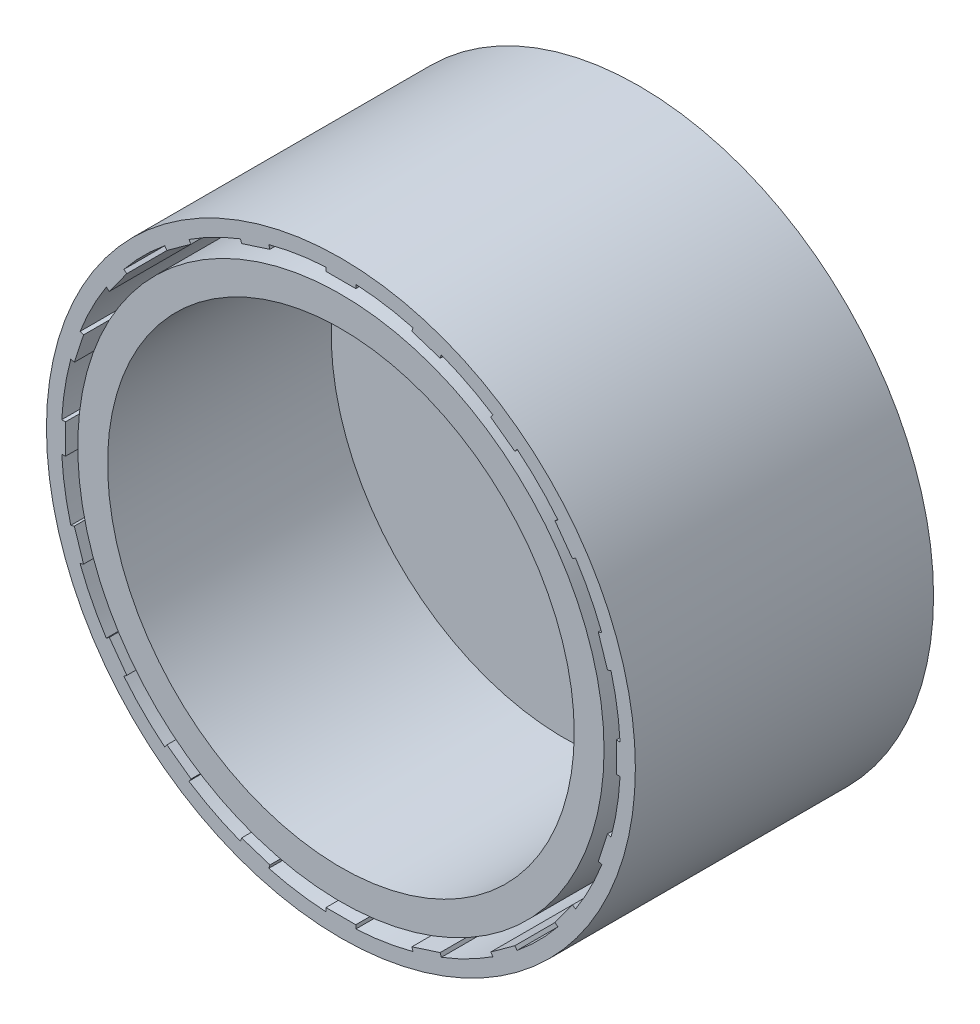
SolidWorks part; units mm, degrees
ref_plane "Front Plane" through (0, 0, 0) normal (0, 0, 1) x (1, 0, 0)
ref_plane "Top Plane" through (0, 0, 0) normal (0, 1, 0) x (1, 0, 0)
ref_plane "Right Plane" through (0, 0, 0) normal (1, 0, 0) x (0, 0, -1)
sketch "Sketch1" plane through (0, 0, 0) normal (0, 0, 1) x (1, 0, 0)
  circle A0 centre (0, 0) radius 18.75
  circle A1 centre (0, 0) radius 17.65
  circle A2 centre (0, 0) radius 4.625
  circle A3 centre (0, 0) radius 1.625
  circle A4 centre (0, 0) radius 19.75
  circle A5 centre (0, 0) radius 15.65
  dimension "D1" = 3.25
  dimension "D2" = 3
  dimension "D3" = 39.5
  dimension "D4" = 1
  dimension "D5" = 1.1
  dimension "D6" = 2
extrude "Boss-Extrude1" add sketch "Sketch1" against normal blind 10 contours A2 A3 region at (-4.4942, 0, 0)
extrude "Boss-Extrude2" add sketch "Sketch1<3>" along normal blind 5 separate body contours A1 A2 | A0 A1 | A4 A0 | A5 A2 | A2 A3 region at (-18.2197, 0, 0) region at (-17.1508, 0, 0) region at (-4.4942, 0, 0) region at (-19.1914, 0, 0) region at (-15.2074, 0, 0)
sketch "Sketch1<3>" plane through (0, 0, 0) normal (0, 0, 1) x (1, 0, 0) same geometry as "Sketch1"
extrude "Boss-Extrude3" add sketch "Sketch1<4>" along normal blind 20 contours A1 A2 | A4 A0 region at (-17.1508, 0, 0) region at (-19.1914, 0, 0)
sketch "Sketch1<4>" plane through (0, 0, 0) normal (0, 0, 1) x (1, 0, 0) same geometry as "Sketch1"
sketch "Sketch2" plane through (0, 0, 0) normal (0, 0, 1) x (1, 0, 0)
  line L0 (4.7575, 17.8782) -> (6.6596, 17.2601)
  line L1 (-1, 18.4733) -> (1, 18.4733)
  line L2 (-1, 18.4733) -> (-1, 18.7233)
  line L3 (-1, 18.7233) -> (1, 18.7233) construction
  line L4 (1, 18.4733) -> (1, 18.7233)
  line L5 (-1, 18.4733) -> (1, 18.7233) construction
  line L6 (-1, 18.7233) -> (1, 18.4733) construction
  line L7 (4.7575, 17.8782) -> (4.8348, 18.1159)
  line L8 (6.6596, 17.2601) -> (6.7369, 17.4979)
  line L9 (10.0493, 15.533) -> (11.6674, 14.3574)
  line L10 (10.0493, 15.533) -> (10.1963, 15.7353)
  line L11 (11.6674, 14.3574) -> (11.8143, 14.5597)
  line L12 (14.3574, 11.6674) -> (15.533, 10.0493)
  line L13 (14.3574, 11.6674) -> (14.5597, 11.8143)
  line L14 (15.533, 10.0493) -> (15.7353, 10.1963)
  line L15 (17.2601, 6.6596) -> (17.8782, 4.7575)
  line L16 (17.2601, 6.6596) -> (17.4979, 6.7369)
  line L17 (17.8782, 4.7575) -> (18.1159, 4.8348)
  line L18 (18.4733, 1) -> (18.4733, -1)
  line L19 (18.4733, 1) -> (18.7233, 1)
  line L20 (18.4733, -1) -> (18.7233, -1)
  line L21 (17.8782, -4.7575) -> (17.2601, -6.6596)
  line L22 (17.8782, -4.7575) -> (18.1159, -4.8348)
  line L23 (17.2601, -6.6596) -> (17.4979, -6.7369)
  line L24 (15.533, -10.0493) -> (14.3574, -11.6674)
  line L25 (15.533, -10.0493) -> (15.7353, -10.1963)
  line L26 (14.3574, -11.6674) -> (14.5597, -11.8143)
  line L27 (11.6674, -14.3574) -> (10.0493, -15.533)
  line L28 (11.6674, -14.3574) -> (11.8143, -14.5597)
  line L29 (10.0493, -15.533) -> (10.1963, -15.7353)
  line L30 (6.6596, -17.2601) -> (4.7575, -17.8782)
  line L31 (6.6596, -17.2601) -> (6.7369, -17.4979)
  line L32 (4.7575, -17.8782) -> (4.8348, -18.1159)
  line L33 (1, -18.4733) -> (-1, -18.4733)
  line L34 (1, -18.4733) -> (1, -18.7233)
  line L35 (-1, -18.4733) -> (-1, -18.7233)
  line L36 (-4.7575, -17.8782) -> (-6.6596, -17.2601)
  line L37 (-4.7575, -17.8782) -> (-4.8348, -18.1159)
  line L38 (-6.6596, -17.2601) -> (-6.7369, -17.4979)
  line L39 (-10.0493, -15.533) -> (-11.6674, -14.3574)
  line L40 (-10.0493, -15.533) -> (-10.1963, -15.7353)
  line L41 (-11.6674, -14.3574) -> (-11.8143, -14.5597)
  line L42 (-14.3574, -11.6674) -> (-15.533, -10.0493)
  line L43 (-14.3574, -11.6674) -> (-14.5597, -11.8143)
  line L44 (-15.533, -10.0493) -> (-15.7353, -10.1963)
  line L45 (-17.2601, -6.6596) -> (-17.8782, -4.7575)
  line L46 (-17.2601, -6.6596) -> (-17.4979, -6.7369)
  line L47 (-17.8782, -4.7575) -> (-18.1159, -4.8348)
  line L48 (-18.4733, -1) -> (-18.4733, 1)
  line L49 (-18.4733, -1) -> (-18.7233, -1)
  line L50 (-18.4733, 1) -> (-18.7233, 1)
  line L51 (-17.8782, 4.7575) -> (-17.2601, 6.6596)
  line L52 (-17.8782, 4.7575) -> (-18.1159, 4.8348)
  line L53 (-17.2601, 6.6596) -> (-17.4979, 6.7369)
  line L54 (-15.533, 10.0493) -> (-14.3574, 11.6674)
  line L55 (-15.533, 10.0493) -> (-15.7353, 10.1963)
  line L56 (-14.3574, 11.6674) -> (-14.5597, 11.8143)
  line L57 (-11.6674, 14.3574) -> (-10.0493, 15.533)
  line L58 (-11.6674, 14.3574) -> (-11.8143, 14.5597)
  line L59 (-10.0493, 15.533) -> (-10.1963, 15.7353)
  line L60 (-6.6596, 17.2601) -> (-4.7575, 17.8782)
  line L61 (-6.6596, 17.2601) -> (-6.7369, 17.4979)
  line L62 (-4.7575, 17.8782) -> (-4.8348, 18.1159)
  circle A0 centre (0, 0) radius 18.75
  circle A1 centre (0, 0) radius 18.75 construction
  point P3 (0, 18.5983)
  point P11 (0, 0)
  point P88 (0, 0)
  dimension "D1" = 2
  dimension "D2" = 0.25
  dimension "D3" = 20
extrude "Boss-Extrude4" add sketch "Sketch2" along normal up to surface (20 mm away) contours L62 A0 L61 L60 | L59 A0 L58 L57 | L4 A0 L2 L1 | L8 A0 L7 L0 | L11 A0 L10 L9 | L14 A0 L13 L12 | L17 A0 L16 L15 | L20 A0 L19 L18 | L23 A0 L22 L21 | L26 A0 L25 L24 | L29 A0 L28 L27 | L32 A0 L31 L30 | L35 A0 L34 L33 | L38 A0 L37 L36 | L41 A0 L40 L39 | L44 A0 L43 L42 | L47 A0 L46 L45 | L50 A0 L49 L48 | L56 A0 L55 L54 | L53 A0 L52 L51 region at (5.75, 17.6966, 0) region at (0, 18.6073, 0) region at (10.9371, 15.0536, 0) region at (-5.75, 17.6966, 0) region at (15.0536, 10.9371, 0) region at (-10.9371, 15.0536, 0) region at (17.6966, 5.75, 0) region at (-15.0536, 10.9371, 0) region at (18.6073, 0, 0) region at (-17.6966, 5.75, 0) region at (17.6966, -5.75, 0) region at (-18.6073, 0, 0) region at (15.0536, -10.9371, 0) region at (-17.6966, -5.75, 0) region at (10.9371, -15.0536, 0) region at (-15.0536, -10.9371, 0) region at (5.75, -17.6966, 0) region at (-10.9371, -15.0536, 0) region at (0, -18.6073, 0) region at (-5.75, -17.6966, 0) up to face at (18.75, 0, 20)
sketch "Sketch3" plane through (0, 0, 0) normal (0, 1, 0) x (1, 0, 0)
  line L0 (0, 10) -> (0, 0) construction
  line L1 (4.625, 10) -> (-4.625, 10) construction
  circle A0 centre (0, 5) radius 2
  dimension "D1" = 4
extrude "Cut-Extrude1" cut sketch "Sketch3" against normal through all
